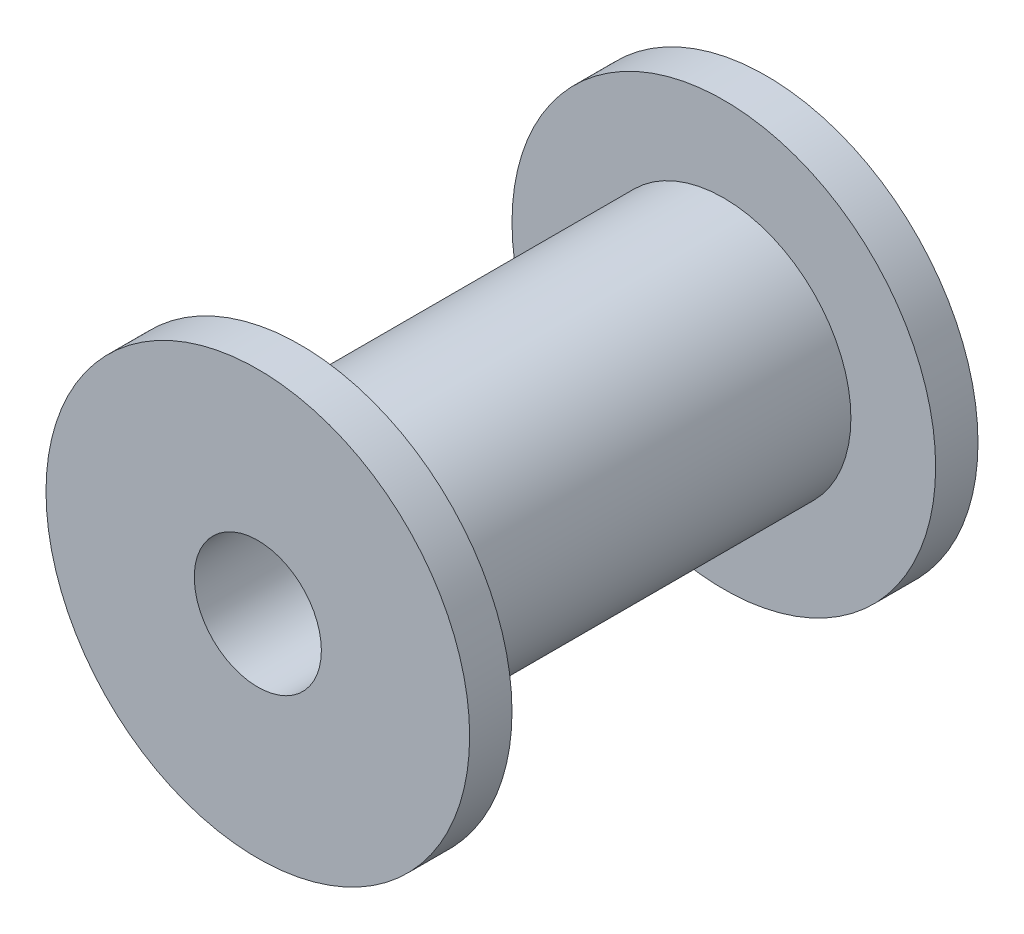
SolidWorks part; units mm, degrees
material "Ti-6Al-4VSolution treated and aged (SS)"
ref_plane "Front Plane" through (0, 0, 0) normal (0, 0, 1) x (1, 0, 0)
ref_plane "Top Plane" through (0, 0, 0) normal (0, 1, 0) x (1, 0, 0)
ref_plane "Right Plane" through (0, 0, 0) normal (1, 0, 0) x (0, 0, -1)
sketch "Sketch1" plane through (0, 0, 0) normal (0, 0, 1) x (1, 0, 0)
  circle A0 centre (0, 0) radius 9.525
  circle A1 centre (0, 0) radius 15.875
  circle A2 centre (0, 0) radius 4.7625
  dimension "D1" = 19.05
  dimension "D2" = 31.75
  dimension "D3" = 9.525
extrude "Boss-Extrude1" add sketch "Sketch1" along normal blind 15.875 contours A0 region at (-9.2556, 0, 0)
extrude "Boss-Extrude2" add sketch "Sketch1<3>" along normal blind 3.175 from surface contours A0 | A1 A0 region at (-9.2556, 0, 0) region at (-15.426, 0, 0) starting at face at (4.7625, 0, 15.875)
sketch "Sketch1<3>" plane through (0, 0, 0) normal (0, 0, 1) x (1, 0, 0) same geometry as "Sketch1"
mirror "Mirror1" about plane through (0, 0, 0) normal (0, 0, 1) of bodies 102
